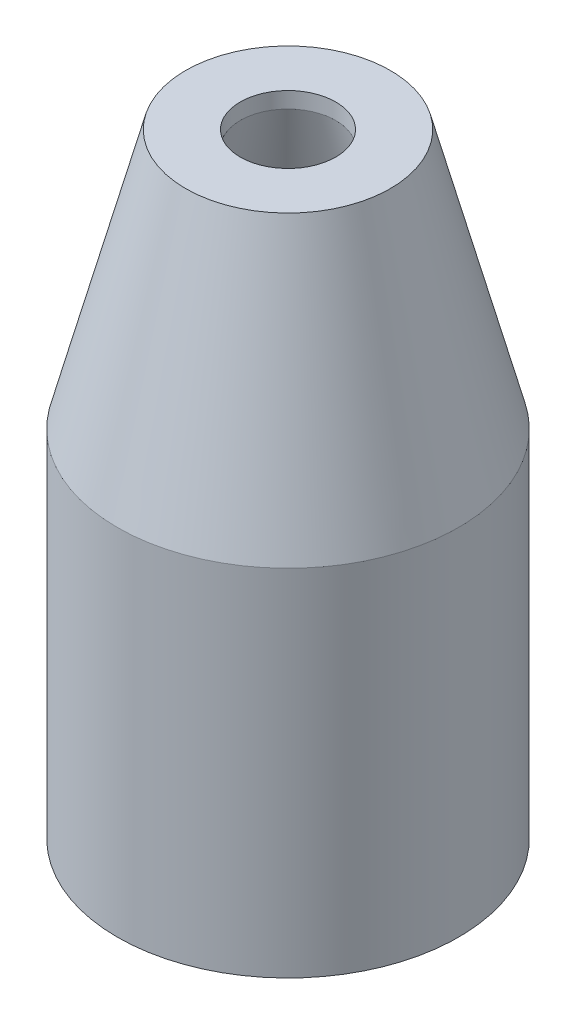
SolidWorks part; units mm, degrees
material "6061 Alloy"
ref_plane "Front Plane" through (0, 0, 0) normal (0, 0, 1) x (1, 0, 0)
ref_plane "Top Plane" through (0, 0, 0) normal (0, 1, 0) x (1, 0, 0)
ref_plane "Right Plane" through (0, 0, 0) normal (1, 0, 0) x (0, 0, -1)
ref_axis "Axis1" through (0, 55, 0) along (0, -1, 0)
sketch "Sketch1" plane through (0, 0, 0) normal (0, 0, 1) x (1, 0, 0)
  line L0 (2.1, 27) -> (4.5, 27)
  line L1 (4.5, 27) -> (7.5, 15.6)
  line L2 (7.5, 15.6) -> (7.5, 0)
  line L3 (7.5, 0) -> (5, 0)
  line L4 (5, 0) -> (5, 15.2766)
  line L5 (5, 15.2766) -> (2.1, 26.2966)
  line L6 (2.1, 26.2966) -> (2.1, 27)
  line L7 (0, 55) -> (0, -55) construction
  point P10 (7.5, 4.3048)
  point P11 (7.5, 15.6)
  point P12 (2.1, 13.6008)
  point P13 (2.1, 21.9235)
  dimension "D1" = 2.5
  dimension "D2" = 2.1
  dimension "D3" = 4.5
  dimension "D4" = 7.5
  dimension "D5" = 15.6
  dimension "D6" = 2.5
  dimension "D7" = 27
revolve "Revolve1" add sketch "Sketch1" angle 360 about axis through (0, 55, 0) along (0, -1, 0)
sketch "Sketch2" plane through (0, 0, 0) normal (0, -1, 0) x (1, 0, 0)
  circle A0 centre (0, 0) radius 5 construction
  circle A1 centre (0, 0) radius 5
curve "Helix/Spiral1" pitch 0.75 height 6 radius 5 centre (0, 0, 0) axis (0, 1, 0) start towards (0, 0, -1)
sketch "Sketch3" plane through (0, 0, 0) normal (1, 0, 0) x (0, 0, -1)
  line L0 (5, 0) -> (5, 0.6)
  line L1 (-7.5, 0) -> (7.5, 0) construction
  line L2 (5, 0.6) -> (5.4, 0.3)
  line L3 (5.4, 0.3) -> (5, 0)
  point P5 (0, 0)
  point P6 (5.6955, 0.3)
  point P7 (0, 0)
  point P8 (0, 0)
  point P9 (5, 0)
  dimension "D1" = 0.6
  dimension "D2" = 0.4
  dimension "D3" = 5.4
sweep "Cut-Sweep1" cut profiles "Sketch3" path "Helix/Spiral1" align with end faces yes
chamfer "Chamfer1" distance 0.5 angle 45 1 edges at (0, 6.3, -5)
